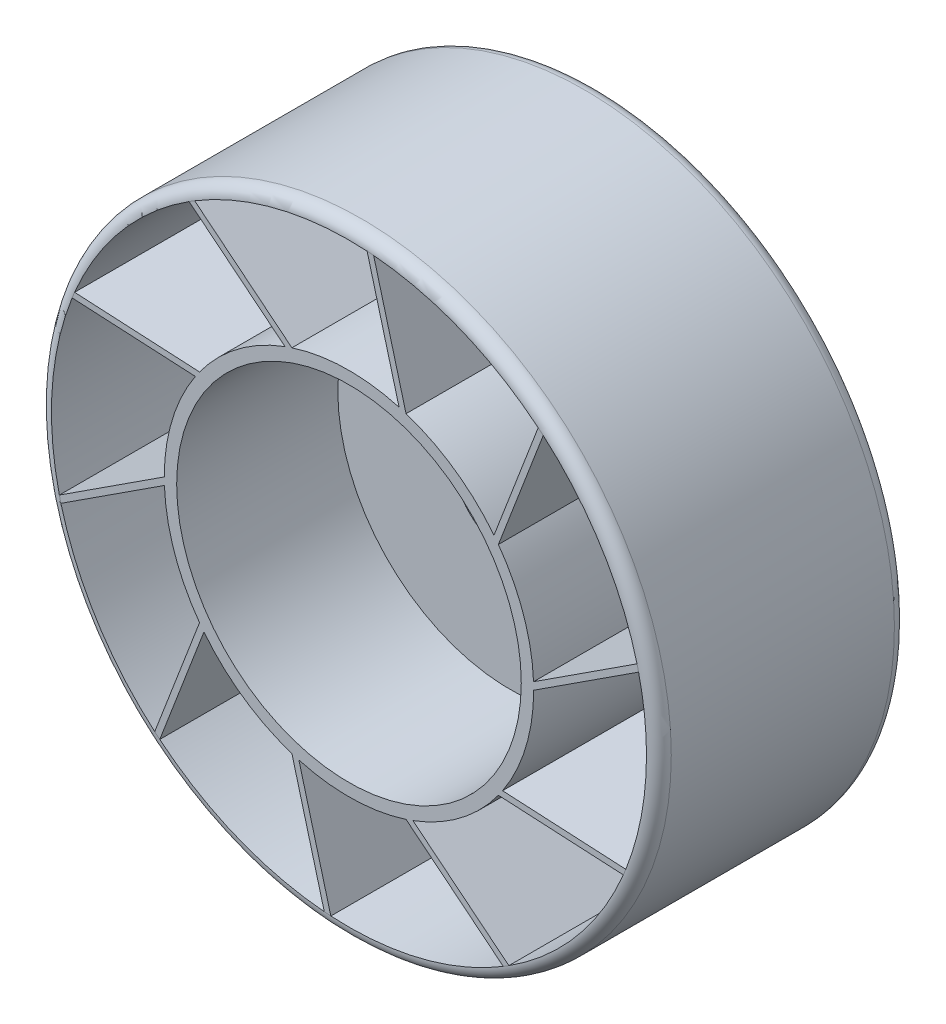
SolidWorks part; units mm, degrees
ref_plane "Front Plane" through (0, 0, 0) normal (0, 0, 1) x (1, 0, 0)
ref_plane "Top Plane" through (0, 0, 0) normal (0, 1, 0) x (1, 0, 0)
ref_plane "Right Plane" through (0, 0, 0) normal (1, 0, 0) x (0, 0, -1)
sketch "Sketch1" plane through (0, 0, 0) normal (0, 0, 1) x (1, 0, 0)
  line L0 (-33.9097, 0) -> (38.3352, 0) construction
  line L1 (0, 26.8691) -> (0, -27.214) construction
  line L2 (14.9, 0) -> (23.362, 5.4972)
  line L3 (14.8884, 0.5887) -> (23.2351, 6.011)
  line L4 (12.391, -8.2749) -> (22.3307, -8.7943)
  line L5 (12.0544, -8.758) -> (22.1314, -9.2845)
  line L6 (5.1606, -13.9778) -> (12.8968, -20.2404)
  line L7 (4.6044, -14.1707) -> (12.4474, -20.5198)
  line L8 (-4.0409, -14.3416) -> (-1.4633, -23.9554)
  line L9 (-4.6044, -14.1707) -> (-1.9911, -23.9173)
  line L10 (-11.6989, -9.2274) -> (-15.2644, -18.5202)
  line L11 (-12.0544, -8.758) -> (-15.6691, -18.1791)
  line L12 (-14.8884, -0.5887) -> (-23.2351, -6.011)
  line L13 (-14.9, 0) -> (-23.362, -5.4972)
  line L14 (-12.391, 8.2749) -> (-22.3307, 8.7943)
  line L15 (-12.0544, 8.758) -> (-22.1314, 9.2845)
  line L16 (-5.1606, 13.9778) -> (-12.8968, 20.2404)
  line L17 (-4.6044, 14.1707) -> (-12.4474, 20.5198)
  line L18 (4.0409, 14.3416) -> (1.4633, 23.9554)
  line L19 (4.6044, 14.1707) -> (1.9911, 23.9173)
  line L20 (11.6989, 9.2274) -> (15.2644, 18.5202)
  line L21 (12.0544, 8.758) -> (15.6691, 18.1791)
  circle A0 centre (0, 0) radius 13.9
  arc A1 (14.8884, 0.5887) -> (12.0544, 8.758) centre (0, 0) ccw
  circle A2 centre (0, 0) radius 25
  arc A3 (23.2351, 6.011) -> (15.6691, 18.1791) centre (0, 0) ccw
  circle A4 centre (0, 0) radius 24 construction
  arc A5 (11.6989, 9.2274) -> (4.6044, 14.1707) centre (0, 0) ccw
  arc A6 (15.2644, 18.5202) -> (1.9911, 23.9173) centre (0, 0) ccw
  arc A7 (1.4633, 23.9554) -> (-12.4474, 20.5198) centre (0, 0) ccw
  arc A8 (4.0409, 14.3416) -> (-4.6044, 14.1707) centre (0, 0) ccw
  arc A9 (-5.1606, 13.9778) -> (-12.0544, 8.758) centre (0, 0) ccw
  arc A10 (-12.8968, 20.2404) -> (-22.1314, 9.2845) centre (0, 0) ccw
  arc A11 (-22.3307, 8.7943) -> (-23.362, -5.4972) centre (0, 0) ccw
  arc A12 (-12.391, 8.2749) -> (-14.9, 0) centre (0, 0) ccw
  arc A13 (-14.8884, -0.5887) -> (-12.0544, -8.758) centre (0, 0) ccw
  arc A14 (-23.2351, -6.011) -> (-15.6691, -18.1791) centre (0, 0) ccw
  arc A15 (-11.6989, -9.2274) -> (-4.6044, -14.1707) centre (0, 0) ccw
  arc A16 (-15.2644, -18.5202) -> (-1.9911, -23.9173) centre (0, 0) ccw
  arc A17 (-4.0409, -14.3416) -> (4.6044, -14.1707) centre (0, 0) ccw
  arc A18 (5.1606, -13.9778) -> (12.0544, -8.758) centre (0, 0) ccw
  arc A19 (12.391, -8.2749) -> (14.9, 0) centre (0, 0) ccw
  arc A20 (12.8968, -20.2404) -> (22.1314, -9.2845) centre (0, 0) ccw
  arc A21 (-1.4633, -23.9554) -> (12.4474, -20.5198) centre (0, 0) ccw
  arc A22 (22.3307, -8.7943) -> (23.362, 5.4972) centre (0, 0) ccw
  dimension "D1" = 27.8
  dimension "D2" = 1
  dimension "D3" = 50
  dimension "D6" = 0.5
  dimension "D4" = 1
  dimension "D5" = 10
extrude "Boss-Extrude1" add sketch "Sketch1" along normal blind 20
fillet "Fillet1" radius 1 2 edges at (25, 0, 0) (25, 0, 20)
sketch "Sketch2" plane through (0, 0, 0) normal (0, 0, -1) x (-1, 0, 0)
  circle A0 centre (0, 0) radius 13.9 construction
  circle A1 centre (0, 0) radius 13.9
extrude "Boss-Extrude2" add sketch "Sketch2" against normal blind 7
sketch "Sketch3" plane through (0, 0, 0) normal (0, 0, -1) x (-1, 0, 0)
  circle A0 centre (0, 0) radius 4.125
  dimension "D1" = 8.25
extrude "Cut-Extrude1" cut sketch "Sketch3" against normal blind 3
sketch "Sketch4" plane through (0, 0, 7) normal (0, 0, 1) x (1, 0, 0)
  circle A0 centre (0, 0) radius 4.6
  dimension "D1" = 9.2
extrude "Cut-Extrude2" cut sketch "Sketch4" against normal blind 2.3
sketch "Sketch7" plane through (0, 0, 3) normal (0, 0, -1) x (-1, 0, 0)
  circle A0 centre (0, 0) radius 1.5
  dimension "D1" = 3
extrude "Cut-Extrude4" [suppressed] cut sketch "Sketch7" against normal blind 2.3
